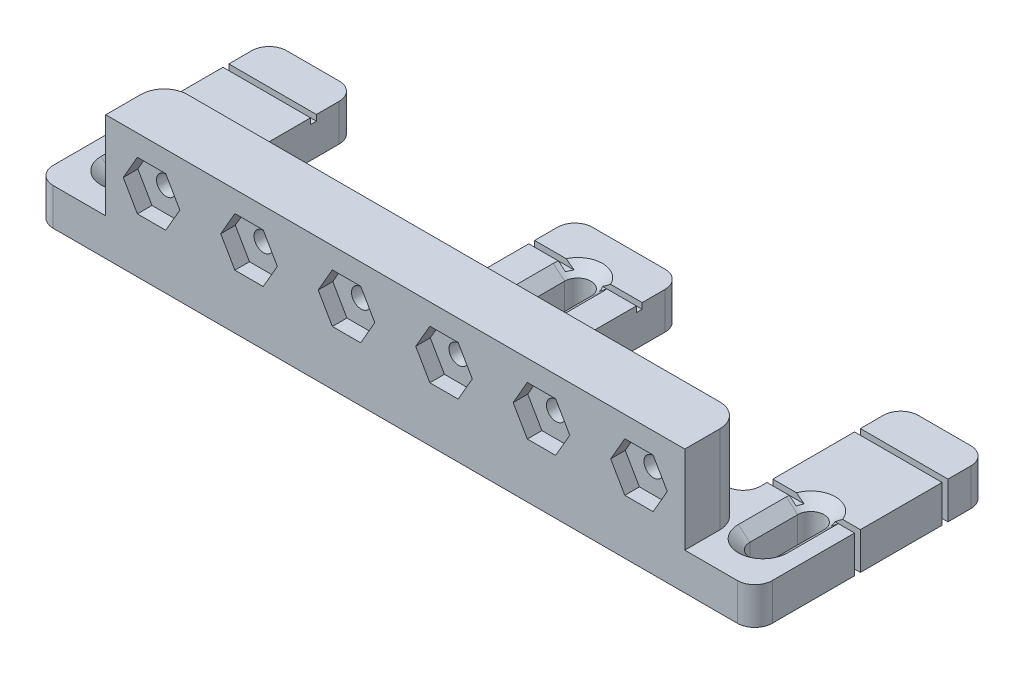
SolidWorks part; units mm, degrees
ref_plane "Front Plane" through (0, 0, 0) normal (0, 0, 1) x (1, 0, 0)
ref_plane "Top Plane" through (0, 0, 0) normal (0, 1, 0) x (1, 0, 0)
ref_plane "Right Plane" through (0, 0, 0) normal (1, 0, 0) x (0, 0, -1)
sketch "Sketch1" plane through (0, 0, 0) normal (0, 1, 0) x (1, 0, 0)
  line L1 (-61.6, -20) -> (0, -20)
  line L2 (-61.6, -20) -> (-61.6, 20)
  line L3 (-61.6, 20) -> (0, 20)
  line L4 (0, -20) -> (0, 20)
  line L5 (-61.6, -20) -> (0, 20) construction
  line L6 (-61.6, 20) -> (0, -20) construction
  point P0 (0, 0)
  dimension "D1" = 61.6
  dimension "D2" = 40
extrude "Boss-Extrude1" add sketch "Sketch1" along normal blind 6.35
hole_wizard "CSK SLOT for #8 Flat Head Machine Screw (100)1" positions "Sketch3" profile "Sketch2" size "#8" standard "ANSI Inch" slot yes end condition up to next
sketch "Sketch3" plane through (0, 6.35, 0) normal (0, 1, 0) x (1, 0, 0)
  line L0 (-54.6, -13.85) -> (-54.6, -1.15) construction
  line L1 (-61.6, 20) -> (-61.6, -20) construction
  line L2 (-61.6, -20) -> (0, -20) construction
  point P0 (-54.6, -7.5)
  dimension "D1" = 12.7
  dimension "D2" = 7
  dimension "D3" = 12.5
sketch "Sketch2" plane through (-54.6, 6.35, 7.5) normal (1, 0, 0) x (0, 0, 1)
  line L0 (0, 0) -> (0, 6.35)
  line L1 (0, 6.35) -> (2.2479, 6.35)
  line L2 (2.2479, 6.35) -> (2.2479, 1.6518)
  line L3 (2.2479, 1.6518) -> (4.2164, 0)
  line L5 (4.2164, 0) -> (0, 0)
  line L6 (-2.2479, 1.6518) -> (-4.2164, 0) construction
  line L11 (0, -6.35) -> (0, 107.95) construction
  dimension "Thru Hole Dia." = 4.4958
  dimension "Thru Hole Depth" = 6.35
  dimension "Near C'Sink Dia." = 8.4328
  dimension "Near C'Sink Angle" = 100
fillet "Fillet1" radius 3 2 edges at (-61.6, 3.175, 20) (-61.6, 3.175, -20)
sketch "Sketch5" plane through (0, 6.35, 0) normal (0, 1, 0) x (1, 0, 0)
  line L0 (-49.6, -20) -> (-49.6, 20) construction
  line L1 (-58.6, -20) -> (0, -20) construction
  line L2 (0, 20) -> (-58.6, 20) construction
  line L3 (-61.6, 17) -> (-61.6, -17) construction
  dimension "D1" = 12
sketch "Sketch4" plane through (0, 0, 0) normal (1, 0, 0) x (0, 0, -1)
  line L2 (-20, 6.35) -> (-10, 6.35)
  line L3 (-20, 6.35) -> (-20, 21.35)
  line L4 (-20, 21.35) -> (-10, 21.35)
  line L5 (-10, 6.35) -> (-10, 21.35)
  dimension "D1" = 10
  dimension "D2" = 15
extrude "Boss-Extrude2" add sketch "Sketch4" against normal up to vertex (49.6 mm away) up to point (-49.6, 6.35, 20)
sketch "Sketch6" plane through (0, 0, 20) normal (0, 0, 1) x (1, 0, 0)
  line L0 (-49.6, 21.35) -> (-49.6, 6.35) construction
  line L1 (-39.3254, 9.35) -> (-36.9005, 13.55)
  line L2 (-36.9005, 13.55) -> (-39.3254, 17.75)
  line L3 (-39.3254, 17.75) -> (-44.1751, 17.75)
  line L4 (-44.1751, 17.75) -> (-46.6, 13.55)
  line L5 (-46.6, 13.55) -> (-44.1751, 9.35)
  line L6 (-44.1751, 9.35) -> (-39.3254, 9.35)
  line L7 (-58.6, 6.35) -> (-49.6, 6.35) construction
  line L11 (-27.4756, 17.75) -> (-29.9005, 13.55)
  line L12 (-29.9005, 13.55) -> (-27.4756, 9.35)
  line L13 (-27.4756, 9.35) -> (-22.6259, 9.35)
  line L14 (-22.6259, 9.35) -> (-20.201, 13.55)
  line L15 (-20.201, 13.55) -> (-22.6259, 17.75)
  line L16 (-22.6259, 17.75) -> (-27.4756, 17.75)
  line L17 (-10.7762, 17.75) -> (-13.201, 13.55)
  line L18 (-13.201, 13.55) -> (-10.7762, 9.35)
  line L19 (-10.7762, 9.35) -> (-5.9264, 9.35)
  line L20 (-5.9264, 9.35) -> (-3.5015, 13.55)
  line L21 (-3.5015, 13.55) -> (-5.9264, 17.75)
  line L22 (-5.9264, 17.75) -> (-10.7762, 17.75)
  circle A0 centre (-41.7503, 13.55) radius 4.2 construction
  circle A1 centre (-25.0508, 13.55) radius 4.2 construction
  circle A2 centre (-8.3513, 13.55) radius 4.2 construction
  point P1 (-49.6, 13.85)
  dimension "D1" = 8.4
  dimension "D2" = 3
  dimension "D3" = 3
  dimension "D4" = 7
  dimension "D5" = 7
extrude "Cut-Extrude1" cut sketch "Sketch6" against normal blind 2.5
sketch "Sketch7" plane through (0, 0, 10) normal (0, 0, -1) x (-1, 0, 0)
  circle A0 centre (8.3513, 13.55) radius 1.65
  circle A1 centre (25.0508, 13.55) radius 1.65
  circle A2 centre (41.7503, 13.55) radius 1.65
  dimension "D1" = 3.3
extrude "Cut-Extrude2" cut sketch "Sketch7" against normal through all both and the other way through all
fillet "Fillet3" radius 4 1 edges at (-49.6, 13.85, 10)
sketch "Ball Cut Plane Distance Setter Sketch" plane through (0, 6.35, 0) normal (0, 1, 0) x (1, 0, 0)
  line L0 (0, -2.4127) -> (-61.6, -2.4127) construction
  line L1 (0, -10) -> (0, 20) construction
  line L2 (-61.6, 17) -> (-61.6, -17) construction
  line L3 (-47.2628, -2.4127) -> (-36.2378, -2.4127) construction
sketch "Ball Cut Plane Slave" plane through (0, 0, 0) normal (0, -1, 0) x (1, 0, 0)
  line L0 (0, 2.4127) -> (-61.6, 2.4127) construction
  line L1 (0, 2.4127) -> (-61.6, 2.4127) construction
ref_plane "Ball Cut Plane" through (0, 0, 2.4127) normal (0, 0, -1) x (-1, 0, 0)
sketch "Sketch13" plane through (0, 0, 2.4127) normal (0, 0, -1) x (-1, 0, 0)
  line L0 (0, 6.35) -> (61.6, 6.35)
  line L1 (61.6, 6.35) -> (61.6, 0)
sketch "Sketch15" plane through (0, 0, 0) normal (1, 0, 0) x (0, 0, -1)
  line L1 (-2.9127, 5.35) -> (-1.9127, 5.35)
  line L2 (-2.9127, 5.35) -> (-2.9127, 7.35)
  line L3 (-2.9127, 7.35) -> (-1.9127, 7.35)
  line L4 (-1.9127, 5.35) -> (-1.9127, 7.35)
  line L5 (-2.9127, 5.35) -> (-1.9127, 7.35) construction
  line L6 (-2.9127, 7.35) -> (-1.9127, 5.35) construction
  point P0 (-2.4127, 6.35)
  dimension "D1" = 1
  dimension "D2" = 2
sweep "Cut-Sweep1" cut profiles "Sketch15" path "Sketch13"
sketch "Max Carbon Length Plane Setter" plane through (0, 6.35, 0) normal (0, 1, 0) x (1, 0, 0)
  line L0 (0, 12.5873) -> (-61.6, 12.5873) construction
  line L1 (0, -1.9127) -> (0, 20) construction
  line L2 (-61.6, 17) -> (-61.6, -1.9127) construction
  line L3 (0, -2.4127) -> (-61.6, -2.4127) construction
  dimension "D1" = 15
sketch "Max Carbon Length Plane Slave" plane through (0, 0, 0) normal (0, -1, 0) x (1, 0, 0)
  line L0 (0, -12.5873) -> (-61.6, -12.5873) construction
  line L1 (-61.6, -17) -> (-61.6, 1.9127) construction
  line L2 (0, -12.5873) -> (-61.6, -12.5873) construction
ref_plane "Max Carbon Length Plane" through (0, 0, -12.5873) normal (0, 0, -1) x (-1, 0, 0)
sketch "Sketch19" plane through (0, 0, -12.5873) normal (0, 0, -1) x (-1, 0, 0)
  line L0 (0, 6.35) -> (61.6, 6.35)
  line L1 (61.6, 6.35) -> (61.6, 0)
sketch "Sketch20" plane through (0, 0, 0) normal (1, 0, 0) x (0, 0, -1)
  line L1 (12.0873, 5.35) -> (13.0873, 5.35)
  line L2 (12.0873, 5.35) -> (12.0873, 7.35)
  line L3 (12.0873, 7.35) -> (13.0873, 7.35)
  line L4 (13.0873, 5.35) -> (13.0873, 7.35)
  line L5 (12.0873, 5.35) -> (13.0873, 7.35) construction
  line L6 (12.0873, 7.35) -> (13.0873, 5.35) construction
  point P0 (12.5873, 6.35)
  dimension "D1" = 1
  dimension "D2" = 2
sweep "Cut-Sweep2" cut profiles "Sketch20" path "Sketch19"
hole_wizard "CSK SLOT for #8 Flat Head Machine Screw (100)2" positions "Sketch22" profile "Sketch21" size "#8" standard "ANSI Inch" slot yes end condition up to next
sketch "Sketch22" plane through (0, 6.35, 0) normal (0, 1, 0) x (1, 0, 0)
  line L0 (0, 0.8262) -> (0, 13.5262) construction
  point P0 (0, 7.1762)
  dimension "D1" = 12.7
sketch "Sketch21" plane through (0, 6.35, -7.1762) normal (1, 0, 0) x (0, 0, 1)
  line L0 (0, 0) -> (0, 6.35)
  line L1 (0, 6.35) -> (2.2479, 6.35)
  line L2 (2.2479, 6.35) -> (2.2479, 1.6518)
  line L3 (2.2479, 1.6518) -> (4.2164, 0)
  line L5 (4.2164, 0) -> (0, 0)
  line L6 (-2.2479, 1.6518) -> (-4.2164, 0) construction
  line L11 (0, -6.35) -> (0, 107.95) construction
  dimension "Thru Hole Dia." = 4.4958
  dimension "Thru Hole Depth" = 6.35
  dimension "Near C'Sink Dia." = 8.4328
  dimension "Near C'Sink Angle" = 100
sketch "Sketch23" plane through (0, 6.35, 0) normal (0, 1, 0) x (1, 0, 0)
  line L0 (0, 20) -> (-58.6, 20) construction
  line L1 (-46.6, 20) -> (-9.2164, 20)
  line L2 (-46.6, 20) -> (-46.6, -4)
  line L3 (-43.6, -7) -> (-12.2164, -7)
  line L4 (-9.2164, 20) -> (-9.2164, -4)
  line L5 (-61.6, 12.0873) -> (-61.6, -1.9127) construction
  line L6 (-4.2164, 3.0741) -> (-4.2164, 11.2783) construction
  line L7 (-45.6, -10) -> (0, -10) construction
  arc A0 (-12.2164, -7) -> (-9.2164, -4) centre (-12.2164, -4) ccw
  arc A1 (-46.6, -4) -> (-43.6, -7) centre (-43.6, -4) ccw
  dimension "D4" = 3
  dimension "D1" = 15
  dimension "D2" = 5
  dimension "D3" = 3
extrude "Cut-Extrude3" cut sketch "Sketch23" against normal through all both and the other way through all
fillet "Fillet4" radius 3 2 edges at (-9.2164, 3.175, -20) (-46.6, 3.175, -20)
mirror "Mirror1" about plane through (0, 6.35, 20) normal (-1, 0, 0) of bodies 114 111
equation "\"hexdist\"= 5mm"
equation "\"hex\"=5"
